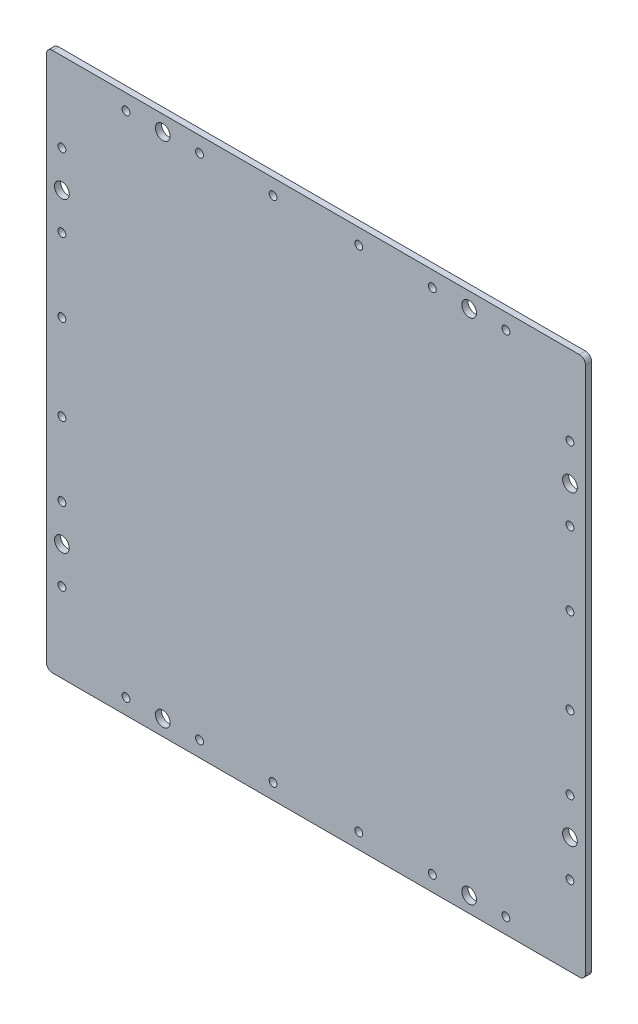
SolidWorks part; units mm, degrees
material "Glass"
ref_plane "Front Plane" through (0, 0, 0) normal (0, 0, 1) x (1, 0, 0)
ref_plane "Top Plane" through (0, 0, 0) normal (0, 1, 0) x (1, 0, 0)
ref_plane "Right Plane" through (0, 0, 0) normal (1, 0, 0) x (0, 0, -1)
sketch "Sketch1" plane through (0, 0, 0) normal (0, 0, 1) x (1, 0, 0)
  line L0 (0, 220) -> (0, -220) construction
  line L1 (-220, 220) -> (220, 220)
  line L2 (-220, 220) -> (-220, -220)
  line L3 (-220, -220) -> (220, -220)
  line L4 (220, 220) -> (220, -220)
  line L5 (-220, 0) -> (220, 0) construction
  dimension "D1" = 440
  dimension "D2" = 440
extrude "Boss-Extrude1" add sketch "Sketch1" along normal blind 5
fillet "Fillet1" radius 5 4 edges at (-220, -220, 2.5) (220, -220, 2.5) (220, 220, 2.5) (-220, 220, 2.5)
sketch "Sketch2" plane through (0, 0, 0) normal (0, 0, -1) x (-1, 0, 0)
  line L0 (-207.3, -155) -> (-207.3, 155) construction
  line L1 (-207.3, 0) -> (0, 0) construction
  line L2 (-220, -215) -> (-220, 215) construction
  circle A0 centre (-207.3, -155) radius 3.2
  circle A1 centre (-207.3, -95) radius 3.2
  circle A2 centre (-207.3, -35) radius 3.2
  circle A3 centre (-207.3, 35) radius 3.2
  circle A4 centre (-207.3, 95) radius 3.2
  circle A5 centre (-207.3, 155) radius 3.2
  dimension "D2" = 6.4
  dimension "D1" = 12.7
  dimension "D3" = 70
  dimension "D4" = 60
  dimension "D5" = 60
extrude "Cut-Extrude1" cut sketch "Sketch2" against normal through all
ref_axis "Axis1" through (0, 0, -0.25) along (0, 0, 1)
pattern_circular "CirPattern1" count 4 over 360 about axis through (0, 0, -0.25) along (0, 0, 1) of "Cut-Extrude1"
sketch "Sketch3" plane through (0, 0, 0) normal (0, 0, -1) x (-1, 0, 0)
  circle A0 centre (207.3, -125) radius 6
  circle A1 centre (207.3, 125) radius 6
  circle A2 centre (207.3, -125) radius 8 construction
  circle A3 centre (207.3, 125) radius 8 construction
  dimension "D1" = 12
extrude "Cut-Extrude2" cut sketch "Sketch3" against normal up to next
pattern_circular "CirPattern2" count 4 over 360 about axis through (0, 0, -0.25) along (0, 0, 1) of "Cut-Extrude2"
